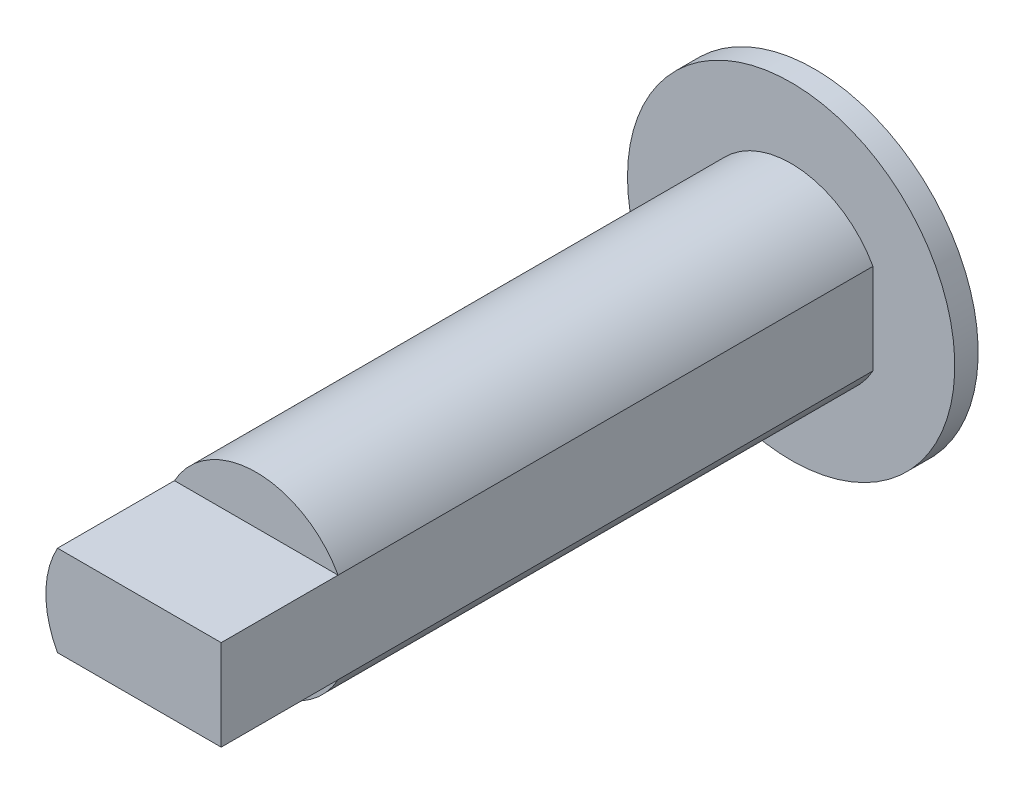
SolidWorks part; units mm, degrees
ref_plane "Front Plane" through (0, 0, 0) normal (0, 0, 1) x (1, 0, 0)
ref_plane "Top Plane" through (0, 0, 0) normal (0, 1, 0) x (1, 0, 0)
ref_plane "Right Plane" through (0, 0, 0) normal (1, 0, 0) x (0, 0, -1)
sketch "Sketch1" plane through (0, 0, 0) normal (0, 0, 1) x (1, 0, 0)
  line L0 (3.5, 1.9365) -> (3.5, -1.9365)
  arc A0 (3.5, 1.9365) -> (3.5, -1.9365) centre (0, 0) ccw
  arc A1 (3.5, -1.9365) -> (3.5, 1.9365) centre (0, 0) ccw construction
  dimension "D1" = 3.5
  dimension "8" = 8
extrude "Boss-Extrude1" add sketch "Sketch1" against normal blind 27.8796
sketch "Sketch2" plane through (0, 0, 0) normal (0, 0, 1) x (1, 0, 0)
  line L0 (3.5, -1.9365) -> (3.5, 1.9365) construction
  line L1 (3.5, -1.9365) -> (3.5, 1.9365) construction
  line L2 (3.5, 1.9365) -> (-3.5, 1.9365)
  line L3 (3.5, -1.9365) -> (-3.5, -1.9365)
  arc A0 (3.5, 1.9365) -> (3.5, -1.9365) centre (0, 0) ccw construction
  arc A1 (3.5, 1.9365) -> (-3.5, 1.9365) centre (0, 0) ccw
  arc A2 (-3.5, 1.9365) -> (-3.5, -1.9365) centre (0, 0) ccw construction
  arc A3 (-3.5, -1.9365) -> (3.5, -1.9365) centre (0, 0) ccw
extrude "Cut-Extrude1" cut sketch "Sketch2" against normal blind 5
sketch "Sketch3" plane through (0, 0, -27.8796) normal (0, 0, -1) x (-1, 0, 0)
  circle A0 centre (0, 0) radius 7
  dimension "D1" = 14
extrude "Boss-Extrude2" add sketch "Sketch3" along normal blind 1
